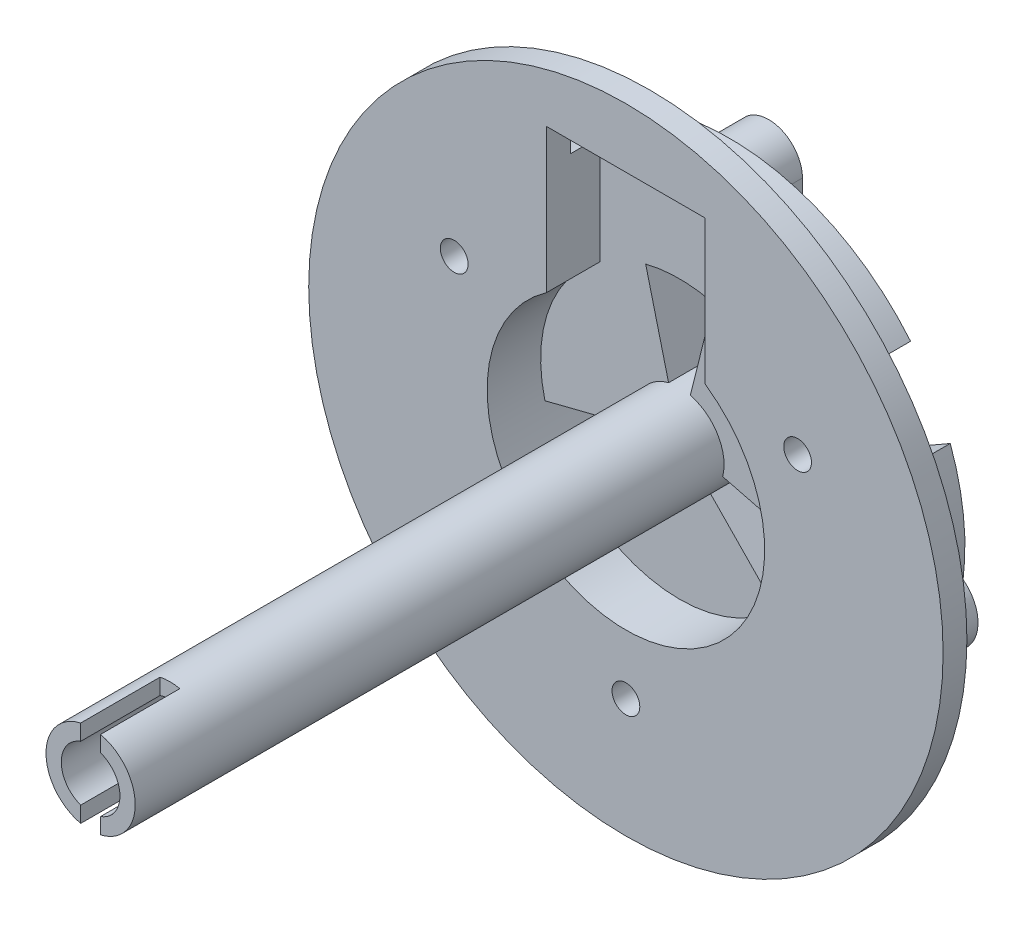
SolidWorks part; units mm, degrees
ref_plane "前视基准面" through (0, 0, 0) normal (0, 0, 1) x (1, 0, 0)
ref_plane "上视基准面" through (0, 0, 0) normal (0, 1, 0) x (1, 0, 0)
ref_plane "右视基准面" through (0, 0, 0) normal (1, 0, 0) x (0, 0, -1)
sketch "草图1" plane through (0, 0, 0) normal (0, 0, 1) x (1, 0, 0)
  circle A0 centre (0, 0) radius 16
extrude "凸台-拉伸1" add sketch "草图1" along normal blind 1.2
sketch "草图2" plane through (0, 0, 1.2) normal (0, 0, 1) x (1, 0, 0)
  circle A0 centre (0, 0) radius 7
extrude "切除-拉伸1" cut sketch "草图2" against normal blind 1.2
sketch "草图3" plane through (0, 0, 1.2) normal (0, 0, 1) x (1, 0, 0)
  circle A2 centre (8.6603, 5) radius 0.7
  circle A3 centre (0, -10) radius 0.7
  circle A4 centre (-8.6603, 5) radius 0.7
extrude "切除-拉伸2" cut sketch "草图3" against normal blind 1.2
sketch "草图4" plane through (0, 0, 0) normal (0, 0, -1) x (-1, 0, 0)
  line L3 (1.7039, 10) -> (1.7039, 5.3952)
  line L16 (-5.5379, -1.0034) -> (-3.6379, -4.2943)
  line L17 (3.6379, -4.2943) -> (5.5379, -1.0034)
  line L18 (1.7039, 5.3952) -> (-1.7039, 5.3952)
  line L19 (-5.5379, -1.0034) -> (-9.6103, -3.3546)
  line L21 (3.6379, -4.2943) -> (7.7103, -6.6454)
  line L25 (-3.6379, -4.2943) -> (-7.7103, -6.6454)
  line L31 (5.5379, -1.0034) -> (9.6103, -3.3546)
  line L32 (-1.7039, 5.3952) -> (-1.7039, 10)
  circle A1 centre (8.6603, -5) radius 0.9
  circle A2 centre (-8.6603, -5) radius 0.9
  circle A3 centre (0, 10) radius 0.9
  arc A4 (1.7039, 10) -> (-1.7039, 10) centre (0, 10) ccw
  arc A5 (7.7103, -6.6454) -> (9.6103, -3.3546) centre (8.6603, -5) ccw
  arc A6 (-9.6103, -3.3546) -> (-7.7103, -6.6454) centre (-8.6603, -5) ccw
extrude "凸台-拉伸2" add sketch "草图4" along normal blind 6
sketch "草图5" plane through (0, 0, 1.2) normal (0, 0, 1) x (1, 0, 0)
  circle A0 centre (0, 0) radius 7
extrude "切除-拉伸3" cut sketch "草图5" against normal blind 11
sketch "草图6" plane through (0, 0, 0) normal (0, 0, -1) x (-1, 0, 0)
  circle A0 centre (0, 0) radius 11.9
  circle A1 centre (0, 0) radius 7
extrude "凸台-拉伸3" add sketch "草图6" along normal blind 4
sketch "草图7" plane through (0, 0, 1.2) normal (0, 0, 1) x (1, 0, 0)
  circle A0 centre (-8.6603, 5) radius 0.7
  circle A1 centre (8.6603, 5) radius 0.7
  circle A2 centre (0, -10) radius 0.7
extrude "切除-拉伸4" cut sketch "草图7" against normal blind 13
sketch "草图8" plane through (0, 0, -4) normal (0, 0, -1) x (-1, 0, 0)
  circle A0 centre (0, 0) radius 2.25
extrude "凸台-拉伸4" add sketch "草图8" against normal blind 33 separate body
sketch "草图9" plane through (0, 0, -4) normal (0, 0, -1) x (-1, 0, 0)
  line L0 (-1.57, -1.6117) -> (-4.8846, -5.0141)
  line L1 (1.57, -1.6117) -> (4.8846, -5.0141)
  line L2 (-2.1808, -0.5539) -> (-6.7846, -1.7232)
  line L3 (-0.5477, 2.1823) -> (-1.7039, 6.7895)
  line L4 (0.5477, 2.1823) -> (1.7039, 6.7895)
  line L5 (2.1808, -0.5539) -> (6.7846, -1.7232)
  arc A0 (-4.8846, -5.0141) -> (4.8846, -5.0141) centre (0, 0) ccw
  arc A1 (-1.7039, 6.7895) -> (-6.7846, -1.7232) centre (0, 0) ccw
  arc A2 (6.7846, -1.7232) -> (1.7039, 6.7895) centre (0, 0) ccw
  arc A3 (2.1808, -0.5539) -> (0.5477, 2.1823) centre (0, 0) ccw
  arc A4 (-1.57, -1.6117) -> (1.57, -1.6117) centre (0, 0) ccw
  arc A5 (-0.5477, 2.1823) -> (-2.1808, -0.5539) centre (0, 0) ccw
extrude "凸台-拉伸5" add sketch "草图9" against normal blind 2.5
sketch "草图10" plane through (0, 0, -4) normal (0, 0, -1) x (-1, 0, 0)
  circle A0 centre (0, 0) radius 1.5
extrude "切除-拉伸5" cut sketch "草图10" against normal blind 33.5
sketch "草图12" plane through (0, 0, 0) normal (1, 0, 0) x (0, 0, -1)
  line L3 (-19.95, -5.0897) -> (-33.7637, -5.0897)
  line L4 (-19.95, -5.0897) -> (-19.95, 5.3715)
  line L5 (-19.95, 5.3715) -> (-33.7637, 5.3715)
  line L6 (-33.7637, -5.0897) -> (-33.7637, 5.3715)
extrude "切除-拉伸6" cut sketch "草图12" against normal mid plane 33.5
sketch "草图13" plane through (0, 0, -4) normal (0, 0, -1) x (-1, 0, 0)
  circle A0 centre (0, -10) radius 2
  circle A1 centre (8.6603, 5) radius 2
  circle A2 centre (-8.6603, 5) radius 2
extrude "切除-拉伸7" cut sketch "草图13" against normal blind 1.5
sketch "草图14" plane through (0, 0, 19.95) normal (0, 0, 1) x (1, 0, 0)
  circle A0 centre (0, 0) radius 1.5
  circle A1 centre (0, 0) radius 2.25
extrude "凸台-拉伸6" add sketch "草图14" along normal blind 8.25
sketch "草图16" plane through (0, 0, -4) normal (0, 0, -1) x (-1, 0, 0)
  line L3 (0, -10) -> (-2, -10)
  line L4 (-2, -10) -> (-2, -14.1303)
  line L5 (-2, -14.1303) -> (2, -14.1303)
  line L6 (2, -14.1303) -> (2, -10)
  line L7 (2, -10) -> (0, -10)
  line L8 (-9.6603, 3.2679) -> (-8.6603, 5)
  line L9 (-8.6603, 5) -> (-7.6603, 6.7321)
  line L10 (-7.6603, 6.7321) -> (-11.2372, 8.7972)
  line L11 (-11.2372, 8.7972) -> (-13.2372, 5.3331)
  line L12 (-13.2372, 5.3331) -> (-9.6603, 3.2679)
  line L13 (7.6603, 6.7321) -> (8.6603, 5)
  line L14 (8.6603, 5) -> (9.6603, 3.2679)
  line L15 (9.6603, 3.2679) -> (13.2372, 5.3331)
  line L16 (13.2372, 5.3331) -> (11.2372, 8.7972)
  line L17 (11.2372, 8.7972) -> (7.6603, 6.7321)
  arc A0 (0.681, -11.8805) -> (-0.681, -11.8805) centre (0, -10) ccw construction
  arc A1 (0.681, -11.8805) -> (-0.681, -11.8805) centre (0, -10) ccw construction
  point P26 (0, 0)
  dimension "D1" = 3
extrude "切除-拉伸9" cut sketch "草图16" against normal blind 1.5
sketch "草图17" plane through (0, 0, 28.2) normal (0, 0, 1) x (1, 0, 0)
  circle A0 centre (0, 0) radius 1.5
  circle A1 centre (0, 0) radius 1.48
extrude "凸台-拉伸7" add sketch "草图17" against normal blind 32.2
sketch "草图15" plane through (0, 0, 28.2) normal (0, 0, 1) x (1, 0, 0)
  line L2 (0.5, 0) -> (0.5, 3.0915)
  line L3 (0.5, 3.0915) -> (-0.5, 3.0915)
  line L4 (-0.5, 3.0915) -> (-0.5, -2.9006)
  line L5 (-0.5, -2.9006) -> (0.5, -2.9006)
  line L6 (0.5, -2.9006) -> (0.5, 0)
extrude "切除-拉伸8" cut sketch "草图15" against normal blind 4
sketch "草图18" plane through (0, 0, 1.2) normal (0, 0, 1) x (1, 0, 0)
  line L0 (0, 13) -> (-4, 13)
  line L2 (-4, 13) -> (-4, 4.7297)
  line L3 (-4, 4.7297) -> (4, 4.7297)
  line L4 (4, 4.7297) -> (4, 13)
  line L5 (4, 13) -> (0, 13)
extrude "切除-拉伸10" cut sketch "草图18" against normal blind 2.7
